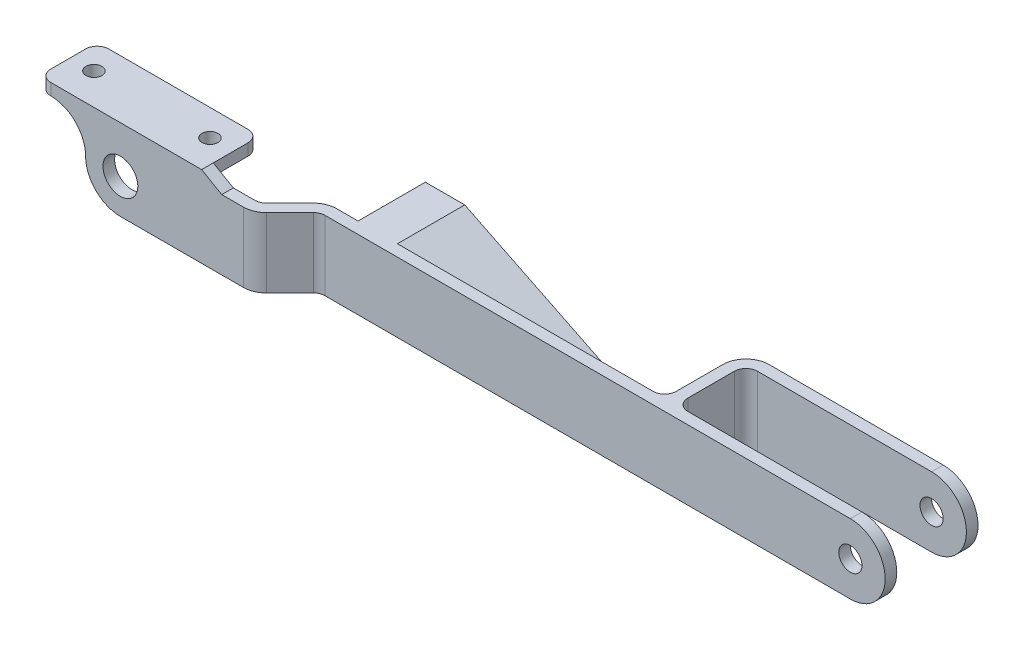
SolidWorks part; units mm, degrees
ref_plane "Front Plane" through (0, 0, 0) normal (0, 0, 1) x (1, 0, 0)
ref_plane "Top Plane" through (0, 0, 0) normal (0, 1, 0) x (1, 0, 0)
ref_plane "Right Plane" through (0, 0, 0) normal (1, 0, 0) x (0, 0, -1)
sketch "Sketch1" plane through (0, 0, 0) normal (0, 0, 1) x (1, 0, 0)
  line L0 (0, 0) -> (381, 0) construction
  line L1 (0, 19.05) -> (381, 19.05)
  line L2 (0, -19.05) -> (381, -19.05)
  line L3 (-19.05, 0) -> (-19.05, 25.4)
  line L4 (-44.45, 25.4) -> (6.35, 25.4)
  line L5 (6.35, 25.4) -> (6.35, 19.05)
  line L6 (38.1, 19.05) -> (-38.1, 19.05) construction
  line L8 (-38.1, 19.05) -> (-44.45, 19.05)
  line L10 (-44.45, 25.4) -> (-44.45, 19.05)
  line L11 (6.35, 25.4) -> (44.45, 25.4)
  line L12 (6.35, 25.4) -> (6.35, 19.05)
  line L13 (6.35, 19.05) -> (44.45, 19.05)
  line L14 (44.45, 25.4) -> (44.45, 19.05)
  arc A0 (0, 19.05) -> (0, -19.05) centre (0, 0) ccw
  arc A1 (381, -19.05) -> (381, 19.05) centre (381, 0) ccw
  circle A2 centre (0, 0) radius 9.525
  circle A3 centre (381, 0) radius 6.35
  arc A4 (-38.1, 19.05) -> (-19.05, 0) centre (-38.1, 0) cw
  point P3 (190.5, 0)
  dimension "D3" = 12.7
  dimension "D4" = 19.05
  dimension "D1" = 381
  dimension "D2" = 44.45
  dimension "D5" = 6.35
  dimension "D6" = 44.45
extrude "Boss-Extrude1" add sketch "Sketch1" along normal blind 6.35 contours L2 A1 L1 A0 A2 A3 | A0 L1 L5 L4 L3 | L8 A4 L3 L4 L10 | L14 L11 L5 L1 region at (-9.0998, 19.8056, 0) region at (192.4787, 0, 0) region at (25.4, 22.225, 0) region at (-29.0002, 19.8056, 0)
sketch "Sketch2" plane through (0, 0, 0) normal (0, 0, -1) x (-1, 0, 0)
  line L1 (44.45, 25.4) -> (-44.45, 25.4)
  line L2 (44.45, 25.4) -> (44.45, 19.05)
  line L3 (44.45, 19.05) -> (-44.45, 19.05)
  line L4 (-44.45, 25.4) -> (-44.45, 19.05)
extrude "Boss-Extrude2" add sketch "Sketch2" along normal blind 25.4
chamfer "Chamfer1" distance 6.35 angle 60 1 edges at (44.45, 19.05, 3.175) first distance on face at (44.45, 21.59, -7.62)
fillet "Fillet1" radius 6.35 3 edges at (44.45, 22.225, -25.4) (-44.45, 22.225, -25.4) (-44.45, 22.225, 6.35)
ref_plane "Plane1" through (0, 0, -18.415) normal (0, 0, -1) x (-1, 0, 0)
sketch "Sketch5" plane through (0, 0, -18.415) normal (0, 0, -1) x (-1, 0, 0)
  line L0 (0, -19.05) -> (-381, -19.05) construction
  line L1 (-55.4485, 19.05) -> (-381, 19.05) construction
  line L2 (-93.5485, -19.05) -> (-381, -19.05)
  line L3 (-93.5485, 19.05) -> (-381, 19.05)
  line L4 (-93.5485, 19.05) -> (-93.5485, -19.05)
  line L5 (-44.45, 25.4) -> (-55.4485, 19.05) construction
  line L6 (-44.45, 25.4) -> (-55.4485, 19.05) construction
  arc A0 (-381, 19.05) -> (-381, -19.05) centre (-381, 0) ccw construction
  arc A1 (-381, 19.05) -> (-381, -19.05) centre (-381, 0) ccw
  circle A2 centre (-381, 0) radius 6.35 construction
  circle A3 centre (-381, 0) radius 6.35
  dimension "D1" = 38.1
extrude "Boss-Extrude4" add sketch "Sketch5" against normal blind 6.35 separate body contours L3 A1 L2 L4 A3 region at (243.2708, 0, -18.415)
sketch "Sketch6" plane through (0, 19.05, 0) normal (0, 1, 0) x (1, 0, 0)
  line L0 (89.0584, 10.2051) -> (76.223, -2.6303)
  line L1 (55.4485, -6.35) -> (381, -6.35) construction
  line L2 (84.5683, 14.6953) -> (71.7329, 1.8599)
  line L3 (55.4485, 0) -> (381, 0) construction
  line L6 (67.2428, -6.35) -> (67.2428, 0)
  line L7 (93.5485, 18.415) -> (93.5485, 12.065)
  line L8 (93.5485, 12.065) -> (381, 12.065) construction
  line L9 (93.5485, 18.415) -> (381, 18.415) construction
  arc A0 (93.5485, 12.065) -> (89.0584, 10.2051) centre (93.5485, 5.715) ccw
  arc A1 (76.223, -2.6303) -> (67.2428, -6.35) centre (67.2428, 6.35) cw
  arc A2 (93.5485, 18.415) -> (84.5683, 14.6953) centre (93.5485, 5.715) ccw
  arc A3 (71.7329, 1.8599) -> (67.2428, 0) centre (67.2428, 6.35) cw
  dimension "D2" = 6.35
  dimension "D4" = 6.35
  dimension "D5" = 12.7
  dimension "D1" = 45
  dimension "D3" = 6.35
extrude "Boss-Extrude5" add sketch "Sketch6" against normal blind 38.1
sketch "Sketch7" plane through (0, 19.05, 0) normal (0, 1, 0) x (1, 0, 0)
  line L0 (89.0584, 10.2051) -> (76.223, -2.6303) construction
  line L1 (89.0584, 10.2051) -> (76.223, -2.6303)
  line L2 (67.2428, -6.35) -> (428.9871, -6.35)
  line L3 (428.9871, -6.35) -> (428.9871, 3.709)
  line L4 (428.9871, 3.709) -> (89.0584, 10.2051)
  arc A0 (67.2428, -6.35) -> (76.223, -2.6303) centre (67.2428, 6.35) ccw construction
  arc A1 (67.2428, -6.35) -> (76.223, -2.6303) centre (67.2428, 6.35) ccw
extrude "Cut-Extrude1" cut sketch "Sketch7" against normal through all
sketch "Sketch8" plane through (0, 0, -18.415) normal (0, 0, -1) x (-1, 0, 0)
  line L0 (-93.5485, 19.05) -> (-381, 19.05) construction
  line L1 (-279.4, 19.05) -> (-273.05, 19.05)
  line L2 (-279.4, 19.05) -> (-279.4, -19.05)
  line L3 (-279.4, -19.05) -> (-273.05, -19.05)
  line L4 (-273.05, 19.05) -> (-273.05, -19.05)
  line L5 (-93.5485, -19.05) -> (-381, -19.05) construction
  circle A0 centre (-381, 0) radius 6.35 construction
  dimension "D1" = 6.35
  dimension "D2" = 101.6
extrude "Boss-Extrude6" add sketch "Sketch8" along normal blind 38.1
sketch "Sketch9" plane through (0, 0, -56.515) normal (0, 0, -1) x (-1, 0, 0)
  line L3 (-381, -19.05) -> (-279.4, -19.05)
  line L4 (-279.4, -19.05) -> (-279.4, 19.05)
  line L5 (-279.4, 19.05) -> (-381, 19.05)
  line L6 (-381, -19.05) -> (-279.4, -19.05)
  line L7 (-279.4, -19.05) -> (-279.4, 19.05)
  line L8 (-279.4, 19.05) -> (-381, 19.05)
  circle A0 centre (-381, 0) radius 6.35 construction
  arc A1 (-381, 19.05) -> (-381, -19.05) centre (-381, 0) ccw
  arc A2 (-381, 19.05) -> (-381, -19.05) centre (-381, 0) ccw
  circle A3 centre (-381, 0) radius 6.35
  line M5 (-279.4, 19.05) -> (-279.4, -19.05)
  line M6 (-279.4, -19.05) -> (-273.05, -19.05)
  line M7 (-273.05, -19.05) -> (-273.05, 19.05)
  line M8 (-273.05, 19.05) -> (-279.4, 19.05)
  dimension "D1" = 0
extrude "Boss-Extrude7" add sketch "Sketch9" along normal blind 6.35 contours L8 A2 L6 M5 | M8 M5 M6 M7 region at (336.4888, 0, -56.515) region at (276.225, 0, -56.515)
fillet "Fillet2" radius 6.35 3 edges at (273.05, 0, -18.415) (279.4, 0, -56.515) (279.4, 0, -18.415)
fillet "Fillet3" radius 12.7 1 edges at (273.05, 0, -62.865)
sketch "Sketch3" plane through (0, 0, -18.415) normal (0, 0, -1) x (-1, 0, 0)
  line L0 (-182.5946, -19.05) -> (-122.6055, 10.5057)
  line L1 (-182.5946, -19.05) -> (-186.8043, -10.5057)
  line L2 (-122.6055, 10.5057) -> (-126.8151, 19.05)
  line L3 (-186.8043, -10.5057) -> (-126.8151, 19.05)
  line L4 (0, -19.05) -> (-67.2428, -19.05) construction
  line L6 (-122.6055, 10.5057) -> (-105.2632, 19.05)
  line L7 (-55.4485, 19.05) -> (-67.2428, 19.05) construction
  line L8 (-105.2632, 19.05) -> (-126.8151, 19.05)
  line L9 (-186.8043, -10.5057) -> (-204.1465, -19.05)
  line L10 (-204.1465, -19.05) -> (-182.5946, -19.05)
  line L11 (-754.225, -205.1187) -> (111.5948, 221.4572) construction
  dimension "D1" = 9.525
  dimension "D2" = 76.2
extrude "Boss-Extrude3" add sketch "Sketch3" along normal offset from surface (36.83 mm away) 1.27 contours L3 L1 L0 L2 | L1 L9 | L2 L6 region at (154.7049, 0, -18.415) region at (191.1818, -16.2019, -18.415) region at (118.2279, 16.2019, -18.415)
sketch "Sketch10" plane through (0, 25.4, 0) normal (0, 1, 0) x (1, 0, 0)
  circle A0 centre (31.75, 10.9141) radius 4.3656 construction
  circle A1 centre (-31.75, 10.9141) radius 4.3656 construction
  circle A2 centre (31.75, 10.9141) radius 4.3656
  circle A3 centre (-31.75, 10.9141) radius 4.3656
extrude "Cut-Extrude2" cut sketch "Sketch10" against normal through all
